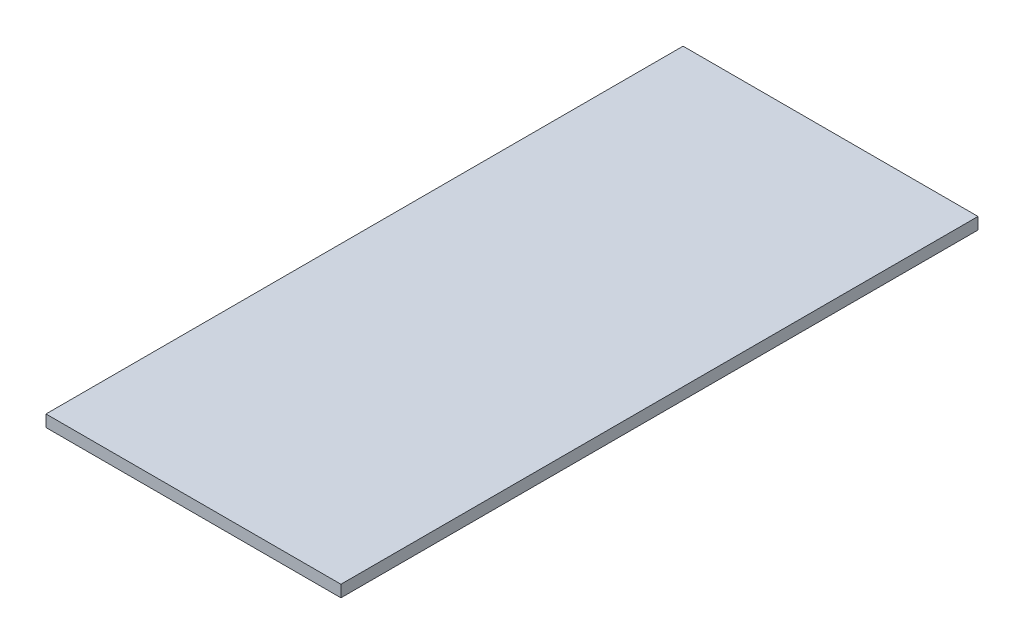
SolidWorks part; units mm, degrees
ref_plane "Front Plane" through (0, 0, 0) normal (0, 0, 1) x (1, 0, 0)
ref_plane "Top Plane" through (0, 0, 0) normal (0, 1, 0) x (1, 0, 0)
ref_plane "Right Plane" through (0, 0, 0) normal (1, 0, 0) x (0, 0, -1)
sketch "Sketch2" plane through (0, 29.1433, 0) normal (0, -1, 0) x (1, 0, 0)
  line L0 (-145.3006, 358.4331) -> (-85.3006, 358.4331) construction
  line L1 (-330.3006, 358.4331) -> (-80.3006, 358.4331)
  line L2 (-330.3006, 358.4331) -> (-330.3006, -181.5669)
  line L3 (-330.3006, -181.5669) -> (-80.3006, -181.5669)
  line L4 (-80.3006, 358.4331) -> (-80.3006, -181.5669)
  line L5 (-145.3006, -181.5669) -> (-85.3006, -181.5669) construction
  line L6 (-80.3006, 358.4331) -> (-80.3006, -181.5669) construction
  line L7 (-330.3006, 358.4331) -> (-330.3006, -181.5669) construction
extrude "Boss-Extrude1" add sketch "Sketch2" along normal blind 10
